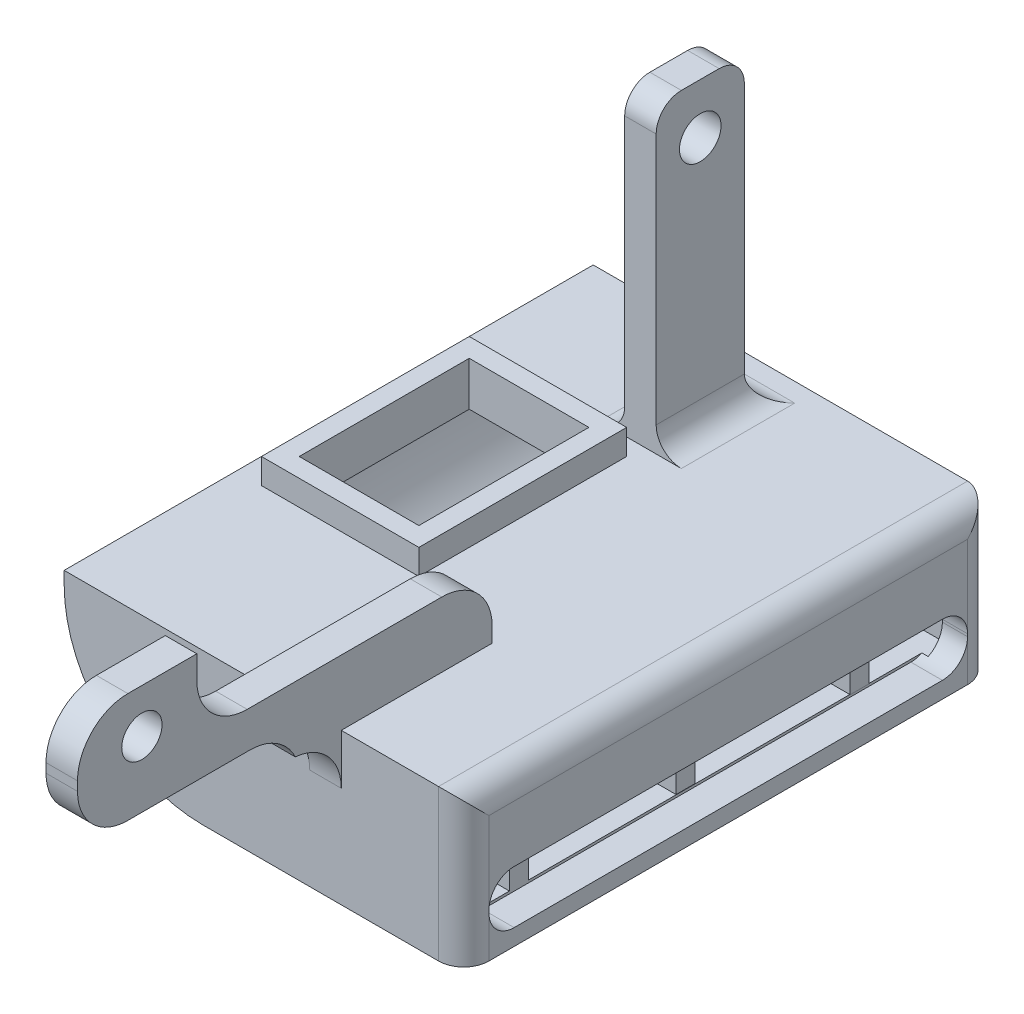
SolidWorks part; units mm, degrees
ref_plane "Alzado" through (0, 0, 0) normal (0, 0, 1) x (1, 0, 0)
ref_plane "Planta" through (0, 0, 0) normal (0, 1, 0) x (1, 0, 0)
ref_plane "Vista lateral" through (0, 0, 0) normal (1, 0, 0) x (0, 0, -1)
sketch "Croquis1" plane through (0, 0, 0) normal (0, 1, 0) x (1, 0, 0)
  line L0 (30.6835, -17.7215) -> (30.6835, -21.7215)
  line L1 (-29.3165, 14.2785) -> (30.6835, 14.2785)
  line L2 (-29.3165, 14.2785) -> (-29.3165, -21.7215)
  line L3 (-29.3165, -21.7215) -> (30.6835, -21.7215)
  line L4 (30.6835, 14.2785) -> (30.6835, 10.2785)
  line L5 (30.6835, 10.2785) -> (2.6835, 10.2785)
  line L7 (30.6835, -17.7215) -> (2.6835, -17.7215)
  line L8 (2.6835, 10.2785) -> (2.6835, -17.7215)
  dimension "D1" = 60
  dimension "D2" = 36
  dimension "D3" = 28
  dimension "D4" = 4
  dimension "D5" = 28
extrude "Saliente-Extruir1" add sketch "Croquis1" along normal blind 12
sketch "Croquis2" plane through (0, 12, 0) normal (0, 1, 0) x (1, 0, 0)
  line L0 (-29.3165, -21.7215) -> (30.6835, -21.7215) construction
  line L1 (-25.8165, 3.9385) -> (-16.3165, 3.9385)
  line L2 (-16.3165, 3.9385) -> (-16.3165, -9.5615)
  line L3 (-25.8165, -9.5615) -> (-16.3165, -9.5615)
  line L4 (-25.8165, 3.9385) -> (-25.8165, -9.5615)
  line L5 (2.6835, 5.4385) -> (-27.3165, 5.4385) construction
  line L6 (2.6835, -17.7215) -> (2.6835, 10.2785) construction
  line L8 (-27.3165, 5.4385) -> (-14.8165, 5.4385)
  line L9 (-27.3165, 5.4385) -> (-27.3165, -11.0615)
  line L10 (-27.3165, -11.0615) -> (-14.8165, -11.0615)
  line L11 (-14.8165, 5.4385) -> (-14.8165, -11.0615)
  dimension "D1" = 1.5
  dimension "D2" = 12.5
  dimension "D3" = 16.5
  dimension "D4" = 10.66
extrude "Saliente-Extruir2" add sketch "Croquis2" along normal blind 2
sketch "Croquis3" plane through (0, 12, 0) normal (0, 1, 0) x (1, 0, 0)
  line L0 (-7.8165, -12.7415) -> (-7.8165, -41.5605)
  line L1 (-9.8165, -12.7415) -> (-7.8165, -12.7415)
  line L2 (-29.3165, 14.2785) -> (-29.3165, -21.7215) construction
  line L3 (-9.8165, -12.7415) -> (-9.8165, -41.5605)
  line L4 (30.6835, 14.2785) -> (-29.3165, 14.2785) construction
  line L7 (-9.8165, -41.5605) -> (-9.8165, -45.6642)
  line L8 (-9.8165, -45.6642) -> (-7.8165, -45.6642)
  line L9 (-7.8165, -41.5605) -> (-7.8165, -45.6642)
  dimension "D1" = 19.5
  dimension "D2" = 27.02
extrude "Saliente-Extruir4" add sketch "Croquis3" along normal blind 11
sketch "Croquis4" plane through (-9.8165, 0, 0) normal (-1, 0, 0) x (0, 0, 1)
  line L0 (-5.4385, 12) -> (40.5515, 12) construction
  line L1 (21.7215, 12) -> (45.6642, 12) construction
  line L2 (40.5515, 12) -> (40.5515, 19.5075) construction
  line L3 (12.7415, 23) -> (12.7415, 12) construction
  circle A0 centre (40.5515, 19.5075) radius 1.6
  dimension "D1" = 27.81
extrude "Cortar-Extruir1" cut sketch "Croquis4" against normal blind 2.5
sketch "Croquis5" plane through (-9.8165, 0, 0) normal (-1, 0, 0) x (0, 0, 1)
  line L0 (28.3713, 14.2761) -> (28.3713, 12)
  line L1 (12.7415, 23) -> (36.1915, 23)
  line L2 (12.7415, 23) -> (12.7415, 17.1784)
  line L3 (12.7415, 17.1784) -> (36.1915, 17.1784)
  line L4 (36.1915, 23) -> (36.1915, 17.1784)
  line L5 (45.6642, 12) -> (28.3713, 12)
  line L6 (45.6642, 12) -> (45.6642, 14.2761)
  line L7 (45.6642, 14.2761) -> (28.3713, 14.2761)
extrude "Cortar-Extruir2" cut sketch "Croquis5" against normal blind 2
sketch "Croquis6" plane through (0, 0, 21.7215) normal (0, 0, 1) x (1, 0, 0)
  line L6 (-29.3165, 0) -> (30.6835, 0)
  line L7 (30.6835, 0) -> (30.6835, 12)
  line L8 (30.6835, 12) -> (-7.8165, 12)
  line L9 (-7.8165, 12) -> (-9.8165, 12)
  line L10 (-9.8165, 12) -> (-29.3165, 12)
  line L11 (-29.3165, 12) -> (-29.3165, 0)
  line L12 (-29.3165, 0) -> (30.6835, 0)
  line L13 (30.6835, 0) -> (30.6835, 12)
  line L14 (30.6835, 12) -> (-7.8165, 12)
  line L15 (-7.8165, 12) -> (-9.8165, 12)
  line L16 (-9.8165, 12) -> (-29.3165, 12)
  line L17 (-29.3165, 12) -> (-29.3165, 0)
  dimension "D1" = 0
extrude "Saliente-Extruir5" add sketch "Croquis6" along normal blind 3
sketch "Croquis7" plane through (0, 0, -14.2785) normal (0, 0, -1) x (-1, 0, 0)
  line L4 (-30.6835, 0) -> (29.3165, 0)
  line L5 (29.3165, 0) -> (29.3165, 12)
  line L6 (29.3165, 12) -> (-30.6835, 12)
  line L7 (-30.6835, 12) -> (-30.6835, 0)
  line L8 (-30.6835, 0) -> (29.3165, 0)
  line L9 (29.3165, 0) -> (29.3165, 12)
  line L10 (29.3165, 12) -> (-30.6835, 12)
  line L11 (-30.6835, 12) -> (-30.6835, 0)
  dimension "D1" = 0
extrude "Saliente-Extruir6" add sketch "Croquis7" along normal blind 3
sketch "Croquis8" plane through (0, 0, 24.7215) normal (0, 0, 1) x (1, 0, 0)
  line L2 (-18.3165, 0) -> (-29.3165, 0)
  line L4 (-29.3165, 0) -> (-29.3165, 11)
  line L5 (-15.3452, 0) -> (-15.2756, 0)
  arc A0 (-18.3165, 0) -> (-29.3165, 11) centre (-18.3165, 11) cw
  line M1 (-29.3165, 12) -> (-29.3165, 0)
  line M2 (-29.3165, 0) -> (30.6835, 0)
  dimension "D1" = 11
extrude "Cortar-Extruir3" cut sketch "Croquis8" against normal blind 42 contours A0 M2 M1 region at (-26.8594, 2.457, 24.7215)
shell "Vaciado4" thickness 1.5 removed face at (-21.0665, 12, 2.8115)
fillet "Redondeo2" radius 4 4 edges at (-8.8165, 12, 24.7215) (-8.8165, 14.2761, 28.3713) (-8.8165, 17.1784, 36.1915) (-8.8165, 17.1784, 12.7415)
fillet "Redondeo3" radius 4 2 edges at (-8.8165, 23, 45.6642) (-8.8165, 14.2761, 45.6642)
sketch "Croquis10" plane through (0, 12, 0) normal (0, 1, 0) x (1, 0, 0)
  line L0 (-29.3165, 17.2785) -> (-29.3165, -24.7215) construction
  line L1 (-13.8165, 13.7785) -> (-16.3165, 13.7785)
  line L2 (-13.8165, 13.7785) -> (-13.8165, 6.7785)
  line L3 (-13.8165, 6.7785) -> (-16.3165, 6.7785)
  line L4 (-16.3165, 13.7785) -> (-16.3165, 6.7785)
  line L5 (-29.3165, 17.2785) -> (30.6835, 17.2785) construction
  dimension "D1" = 7
  dimension "D2" = 2.5
  dimension "D3" = 13
  dimension "D4" = 3.5
extrude "Saliente-Extruir8" add sketch "Croquis10" along normal blind 24
sketch "Croquis11" plane through (-16.3165, 0, 0) normal (-1, 0, 0) x (0, 0, 1)
  line L0 (-10.2785, 36) -> (-10.2785, 12) construction
  line L1 (-13.7785, 36) -> (-6.7785, 36) construction
  line L2 (-13.7785, 12) -> (-6.7785, 12) construction
  line L3 (-10.2785, 12) -> (-10.2785, 32.0033) construction
  circle A0 centre (-10.2785, 32.0033) radius 1.65
extrude "Cortar-Extruir4" cut sketch "Croquis11" against normal blind 2.5
sketch "Croquis14" plane through (-7.8165, 0, 0) normal (1, 0, 0) x (0, 0, -1)
  line L8 (-36.1915, 23) -> (-41.6642, 23)
  line L9 (-45.6642, 19) -> (-45.6642, 18.2761)
  line L10 (-41.6642, 14.2761) -> (-31.9808, 14.2761)
  line L11 (-24.7215, 8.0154) -> (-24.7215, 12)
  line L12 (-24.7215, 12) -> (-12.7415, 12)
  line L13 (-12.7415, 12) -> (-12.7415, 13.1784)
  line L14 (-16.7415, 17.1784) -> (-32.1915, 17.1784)
  line L15 (-36.1915, 21.1784) -> (-36.1915, 23)
  line L16 (-36.1915, 23) -> (-41.6642, 23)
  line L17 (-45.6642, 19) -> (-45.6642, 18.2761)
  line L18 (-41.6642, 14.2761) -> (-31.9808, 14.2761)
  line L19 (-24.7215, 8.0154) -> (-24.7215, 12)
  line L20 (-24.7215, 12) -> (-12.7415, 12)
  line L21 (-12.7415, 12) -> (-12.7415, 13.1784)
  line L22 (-16.7415, 17.1784) -> (-32.1915, 17.1784)
  line L23 (-36.1915, 21.1784) -> (-36.1915, 23)
  circle A0 centre (-40.5515, 19.5075) radius 1.6 construction
  circle A1 centre (-40.5515, 19.5075) radius 1.6
  arc A7 (-41.6642, 23) -> (-45.6642, 19) centre (-41.6642, 19) ccw
  arc A8 (-45.6642, 18.2761) -> (-41.6642, 14.2761) centre (-41.6642, 18.2761) ccw
  arc A9 (-28.3713, 12) -> (-31.9808, 14.2761) centre (-31.9808, 10.2761) ccw
  arc A10 (-24.7215, 8.0154) -> (-28.3713, 12) centre (-28.7215, 8.0154) ccw
  arc A12 (-12.7415, 13.1784) -> (-16.7415, 17.1784) centre (-16.7415, 13.1784) ccw
  arc A13 (-36.1915, 21.1784) -> (-32.1915, 17.1784) centre (-32.1915, 21.1784) ccw
  arc A14 (-41.6642, 23) -> (-45.6642, 19) centre (-41.6642, 19) ccw
  arc A15 (-45.6642, 18.2761) -> (-41.6642, 14.2761) centre (-41.6642, 18.2761) ccw
  arc A16 (-28.3713, 12) -> (-31.9808, 14.2761) centre (-31.9808, 10.2761) ccw
  arc A17 (-24.7215, 8.0154) -> (-28.3713, 12) centre (-28.7215, 8.0154) ccw
  arc A19 (-12.7415, 13.1784) -> (-16.7415, 17.1784) centre (-16.7415, 13.1784) ccw
  arc A20 (-36.1915, 21.1784) -> (-32.1915, 17.1784) centre (-32.1915, 21.1784) ccw
  dimension "D1" = 0
extrude "Saliente-Extruir10" add sketch "Croquis14" along normal blind 0.5
sketch "Croquis15" plane through (0, 12, 0) normal (0, 1, 0) x (1, 0, 0)
  line L0 (30.6835, -24.7215) -> (-7.3165, -24.7215) construction
  line L1 (2.4073, -24.7215) -> (30.6835, -24.7215)
  line L2 (2.4073, -24.7215) -> (2.4073, 17.2785)
  line L3 (2.4073, 17.2785) -> (30.6835, 17.2785)
  line L4 (30.6835, -24.7215) -> (30.6835, 17.2785)
extrude "Cortar-Extruir5" cut sketch "Croquis15" against normal blind 12
sketch "Croquis16" plane through (2.4073, 0, 0) normal (1, 0, 0) x (0, 0, -1)
  line L1 (-24.7215, 12) -> (17.2785, 12)
  line L2 (-24.7215, 12) -> (-24.7215, 0)
  line L3 (-24.7215, 0) -> (17.2785, 0)
  line L4 (17.2785, 12) -> (17.2785, 0)
extrude "Saliente-Extruir11" add sketch "Croquis16" against normal blind 2
sketch "Croquis18" plane through (2.4073, 0, 0) normal (1, 0, 0) x (0, 0, -1)
  line L0 (-24.7215, 6) -> (17.2785, 6) construction
  line L1 (-24.7215, 0) -> (-24.7215, 12) construction
  line L2 (17.2785, 0) -> (17.2785, 12) construction
  line L3 (17.2785, 6) -> (-3.7215, 6) construction
  line L4 (-3.7215, 6) -> (-3.7215, 0) construction
  line L5 (17.2785, 0) -> (-24.7215, 0) construction
  line L6 (-3.7215, 0) -> (-3.7215, 12) construction
  line L7 (17.2785, 12) -> (-24.7215, 12) construction
  line L9 (-20.7215, 5.5) -> (13.2785, 5.5)
  line L10 (-22.7215, 3.5) -> (-22.7215, 3.3)
  line L11 (-20.7215, 1.3) -> (13.2785, 1.3)
  line L12 (15.2785, 3.5) -> (15.2785, 3.3)
  arc A0 (15.2785, 3.5) -> (13.2785, 5.5) centre (13.2785, 3.5) ccw
  arc A1 (15.2785, 3.3) -> (13.2785, 1.3) centre (13.2785, 3.3) cw
  arc A2 (-22.7215, 3.3) -> (-20.7215, 1.3) centre (-20.7215, 3.3) ccw
  arc A3 (-22.7215, 3.5) -> (-20.7215, 5.5) centre (-20.7215, 3.5) cw
  point P19 (15.2785, 5.5)
  point P22 (15.2785, 1.3)
  point P27 (-22.7215, 5.5)
  dimension "D6" = 2
  dimension "D1" = 38
  dimension "D2" = 4.2
  dimension "D3" = 2
  dimension "D4" = 2
  dimension "D5" = 6.5
extrude "Cortar-Extruir6" cut sketch "Croquis18" against normal blind 2.5
sketch "Croquis19" plane through (0, 1.5, 0) normal (0, 1, 0) x (1, 0, 0)
  line L0 (-18.3165, 15.7785) -> (-18.3165, -23.2215) construction
  line L1 (-18.3165, -18.5961) -> (-0.0927, -18.5961)
  line L2 (-18.3165, -18.5961) -> (-18.3165, -17.0961)
  line L3 (-18.3165, -17.0961) -> (-0.0927, -17.0961)
  line L4 (-0.0927, -18.5961) -> (-0.0927, -17.0961)
  line L5 (-0.0927, -21.5933) -> (-0.0927, 14.1503) construction
  line L6 (-18.3361, -5.3453) -> (-0.1124, -5.3453)
  line L7 (-18.3361, -5.3453) -> (-18.3361, -3.8453)
  line L8 (-18.3361, -3.8453) -> (-0.1124, -3.8453)
  line L9 (-0.1124, -5.3453) -> (-0.1124, -3.8453)
  line L10 (-18.2876, 8.4292) -> (-0.0638, 8.4292)
  line L11 (-18.2876, 8.4292) -> (-18.2876, 9.9292)
  line L12 (-18.2876, 9.9292) -> (-0.0638, 9.9292)
  line L13 (-0.0638, 8.4292) -> (-0.0638, 9.9292)
  dimension "D1" = 1.5
extrude "Saliente-Extruir16" add sketch "Croquis19" along normal up to surface (9 mm away)
fillet "Redondeo4" radius 2 3 edges at (2.4073, 6, 24.7215) (2.4073, 6, -17.2785) (2.4073, 12, 3.7215)
fillet "Redondeo5" radius 2 2 edges at (-15.0665, 36, -6.7785) (-15.0665, 36, -13.7785)
fillet "Redondeo6" radius 2 3 edges at (-16.3165, 12, -10.2785) (-15.0665, 12, -13.7785) (-13.8165, 12, -10.2785)
